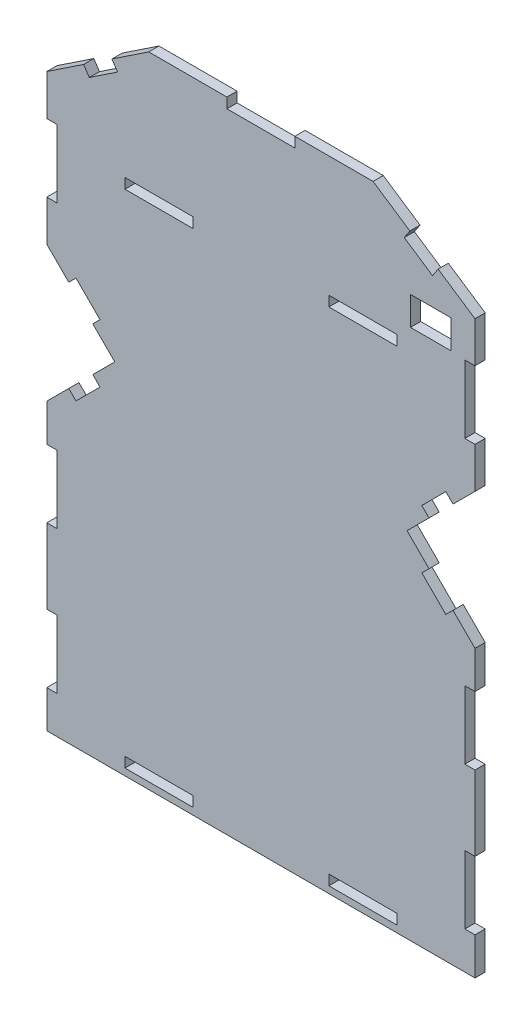
SolidWorks part; units mm, degrees
ref_plane "Front Plane" through (0, 0, 0) normal (0, 0, 1) x (1, 0, 0)
ref_plane "Top Plane" through (0, 0, 0) normal (0, 1, 0) x (1, 0, 0)
ref_plane "Right Plane" through (0, 0, 0) normal (1, 0, 0) x (0, 0, -1)
sketch "Sketch1" plane through (0, 0, 0) normal (0, 0, 1) x (1, 0, 0)
  line L0 (62.2747, 0) -> (62.2747, -11)
  line L1 (-33.7253, 104) -> (-10.7253, 104)
  line L2 (-63.7253, 84) -> (-63.7253, 72)
  line L3 (-63.7253, -84) -> (62.2747, -84)
  line L4 (62.2747, 84) -> (62.2747, 72)
  line L5 (-0.7253, -84) -> (-0.7253, -49.3815) construction
  line L6 (-63.7253, -84) -> (-63.7253, -80.5) construction
  line L7 (-63.7253, -80.5) -> (-60.7253, -80.5) construction
  line L8 (-63.7253, 84) -> (-52.8856, 91.2265)
  line L10 (-63.7253, 84) -> (-63.7253, 72) construction
  line L11 (-60.7253, -80.5) -> (-60.7253, -84) construction
  line L12 (-63.7253, 0) -> (-57.2608, 6.4645)
  line L13 (-43.7253, 20) -> (-50.1898, 26.4645)
  line L14 (62.2747, 0) -> (55.8102, 6.4645)
  line L15 (42.2747, 20) -> (48.7392, 26.4645)
  line L16 (-63.7253, 0) -> (-63.7253, -11)
  line L17 (62.2747, -80.5) -> (59.2747, -80.5) construction
  line L18 (-60.7253, -80.5) -> (59.2747, -80.5) construction
  line L19 (-0.7253, -80.5) -> (-60.7253, -80.5) construction
  line L20 (19.2747, -82) -> (19.2747, -79)
  line L21 (-40.7253, -82) -> (-20.7253, -82)
  line L22 (-40.7253, -82) -> (-40.7253, -79)
  line L23 (-40.7253, -79) -> (-20.7253, -79)
  line L24 (-20.7253, -82) -> (-20.7253, -79)
  line L25 (-40.7253, -82) -> (-20.7253, -79) construction
  line L26 (-40.7253, -79) -> (-20.7253, -82) construction
  line L27 (39.2747, -82) -> (19.2747, -82)
  line L28 (39.2747, -82) -> (39.2747, -79)
  line L29 (39.2747, -79) -> (19.2747, -79)
  line L30 (-63.7253, -84) -> (-62.221, -84) construction
  line L31 (-63.7253, -42) -> (-62.2253, -42) construction
  line L32 (-62.2253, -42) -> (-62.2253, 0) construction
  line L33 (-62.2253, 0) -> (-63.7253, 0) construction
  line L34 (-63.7253, -31) -> (-60.7253, -31)
  line L36 (-63.7253, -11) -> (-60.7253, -11)
  line L37 (-60.7253, -31) -> (-60.7253, -11)
  line L38 (-63.7253, -31) -> (-60.7253, -11) construction
  line L39 (-63.7253, -11) -> (-60.7253, -31) construction
  line L40 (-63.7253, -53) -> (-60.7253, -53)
  line L41 (-60.7253, -53) -> (-60.7253, -73)
  line L42 (-63.7253, -73) -> (-60.7253, -73)
  line L43 (-62.2253, -84) -> (-63.7253, -84) construction
  line L44 (62.2747, -53) -> (59.2747, -53)
  line L45 (59.2747, -53) -> (59.2747, -73)
  line L46 (62.2747, -73) -> (59.2747, -73)
  line L47 (62.2747, -31) -> (59.2747, -31)
  line L48 (62.2747, -11) -> (59.2747, -11)
  line L49 (59.2747, -31) -> (59.2747, -11)
  line L50 (-63.7253, -73) -> (-63.7253, -84)
  line L51 (62.2747, -73) -> (62.2747, -84)
  line L52 (62.2747, -31) -> (62.2747, -53)
  line L53 (-63.7253, -31) -> (-63.7253, -53)
  line L54 (-63.7253, 40) -> (-62.2253, 40) construction
  line L55 (-62.2253, 40) -> (-62.2253, 84) construction
  line L56 (-62.2253, 84) -> (-63.7253, 84) construction
  line L57 (-63.7253, 52) -> (-63.7253, 40)
  line L58 (-63.7253, 52) -> (-60.7253, 52)
  line L60 (-63.7253, 72) -> (-60.7253, 72)
  line L61 (-60.7253, 52) -> (-60.7253, 72)
  line L62 (-63.7253, 52) -> (-60.7253, 72) construction
  line L63 (-63.7253, 72) -> (-60.7253, 52) construction
  line L64 (-63.7253, 52) -> (-63.7253, 40) construction
  line L65 (62.2747, 52) -> (59.2747, 52)
  line L66 (59.2747, 52) -> (59.2747, 72)
  line L67 (62.2747, 72) -> (59.2747, 72)
  line L68 (62.2747, 52) -> (62.2747, 40)
  line L69 (-43.7253, 20) -> (-42.6646, 18.9393) construction
  line L70 (-63.7253, 0) -> (-62.6646, -1.0607) construction
  line L71 (-62.6646, -1.0607) -> (-42.6646, 18.9393) construction
  line L72 (-55.1395, 4.3431) -> (-57.2608, 6.4645)
  line L73 (-55.1395, 4.3431) -> (-48.0685, 11.4142)
  line L75 (-48.0685, 11.4142) -> (-50.1898, 13.5355)
  line L76 (-50.1898, 13.5355) -> (-43.7253, 20)
  line L77 (53.6889, 4.3431) -> (55.8102, 6.4645)
  line L78 (46.6178, 11.4142) -> (48.7392, 13.5355)
  line L79 (53.6889, 4.3431) -> (46.6178, 11.4142)
  line L80 (42.2747, 20) -> (5.8268, 20) construction
  line L81 (-55.1395, 35.6569) -> (-57.2608, 33.5355)
  line L82 (-48.0685, 28.5858) -> (-50.1898, 26.4645)
  line L83 (-55.1395, 35.6569) -> (-48.0685, 28.5858)
  line L84 (-57.2608, 33.5355) -> (-63.7253, 40)
  line L85 (46.6178, 28.5858) -> (48.7392, 26.4645)
  line L86 (53.6889, 35.6569) -> (55.8102, 33.5355)
  line L87 (53.6889, 35.6569) -> (46.6178, 28.5858)
  line L88 (55.8102, 33.5355) -> (62.2747, 40)
  line L89 (48.7392, 13.5355) -> (42.2747, 20)
  line L90 (-63.7253, 84) -> (-52.8856, 91.2265) construction
  line L92 (-52.8856, 91.2265) -> (-51.2215, 88.7303)
  line L93 (-44.5651, 96.7735) -> (-42.901, 94.2774)
  line L94 (-51.2215, 88.7303) -> (-42.901, 94.2774)
  line L95 (-44.5651, 96.7735) -> (-33.7253, 104)
  line L96 (-44.5651, 96.7735) -> (-33.7253, 104) construction
  line L97 (-33.7253, 104) -> (-63.7253, 84) construction
  line L98 (-48.7253, 94) -> (-47.0612, 91.5038) construction
  line L99 (51.4349, 91.2265) -> (49.7708, 88.7303)
  line L100 (49.7708, 88.7303) -> (41.4503, 94.2774)
  line L101 (43.1144, 96.7735) -> (41.4503, 94.2774)
  line L102 (32.2747, 104) -> (43.1144, 96.7735)
  line L103 (62.2747, 84) -> (51.4349, 91.2265)
  line L104 (-33.7253, 104) -> (-33.7253, 102.5) construction
  line L105 (-33.7253, 102.5) -> (32.2747, 102.5) construction
  line L106 (32.2747, 102.5) -> (32.2747, 104) construction
  line L107 (-10.7253, 101) -> (9.2747, 101)
  line L108 (-10.7253, 101) -> (-10.7253, 104)
  line L110 (9.2747, 101) -> (9.2747, 104)
  line L111 (-10.7253, 101) -> (9.2747, 104) construction
  line L112 (-10.7253, 104) -> (9.2747, 101) construction
  line L113 (9.2747, 104) -> (32.2747, 104)
  line L114 (-63.7253, 84) -> (62.2747, 84) construction
  line L115 (-0.7253, 84) -> (-0.7253, 67) construction
  line L116 (-0.7253, 67) -> (-60.7253, 67) construction
  line L117 (39.2747, 65.5) -> (39.2747, 68.5)
  line L118 (-40.7253, 65.5) -> (-20.7253, 65.5)
  line L119 (-40.7253, 65.5) -> (-40.7253, 68.5)
  line L120 (-40.7253, 68.5) -> (-20.7253, 68.5)
  line L121 (-20.7253, 65.5) -> (-20.7253, 68.5)
  line L122 (-40.7253, 65.5) -> (-20.7253, 68.5) construction
  line L123 (-40.7253, 68.5) -> (-20.7253, 65.5) construction
  line L124 (39.2747, 65.5) -> (19.2747, 65.5)
  line L125 (19.2747, 65.5) -> (19.2747, 68.5)
  line L126 (39.2747, 68.5) -> (19.2747, 68.5)
  line L127 (59.2747, 68.5) -> (59.2747, 76.5) construction
  line L128 (59.2747, 84) -> (59.2747, 72) construction
  line L129 (59.2747, 68.5) -> (49.2747, 68.5) construction
  line L130 (39.2747, 68.5) -> (59.2747, 68.5) construction
  line L131 (49.2747, 68.5) -> (49.2747, 76.5) construction
  line L132 (49.2747, 76.5) -> (59.2747, 76.5) construction
  line L134 (43.2747, 80.7) -> (55.2747, 80.7)
  line L135 (43.2747, 80.7) -> (43.2747, 72.3)
  line L136 (43.2747, 72.3) -> (55.2747, 72.3)
  line L137 (55.2747, 80.7) -> (55.2747, 72.3)
  line L138 (43.2747, 80.7) -> (55.2747, 72.3) construction
  line L139 (43.2747, 72.3) -> (55.2747, 80.7) construction
  point P0 (0, 0)
  point P20 (-30.7253, -80.5)
  point P31 (-62.2253, -21)
  point P53 (-62.2253, 62)
  point P67 (-52.6646, 8.9393)
  point P94 (-0.7253, 102.5)
  point P103 (-30.7253, 67)
  dimension "D1" = 84
  dimension "D2" = 126
  dimension "D3" = 20
  dimension "D4" = 30
  dimension "D5" = 20
  dimension "D6" = 20
  dimension "D7" = 44
  dimension "D8" = 20
  dimension "D9" = 30
  dimension "D10" = 20
  dimension "D11" = 20
  dimension "D12" = 84
  dimension "D13" = 44
  dimension "D14" = 20
  dimension "D15" = 3
  dimension "D16" = 3.5
  dimension "D17" = 20
  dimension "D18" = 3
  dimension "D19" = 1.5
  dimension "D20" = 20
  dimension "D21" = 3
  dimension "D22" = 1.5
  dimension "D23" = 1.5
  dimension "D24" = 20
  dimension "D25" = 3
  dimension "D26" = 10
  dimension "D27" = 1.5
  dimension "D28" = 48.0685
  dimension "D29" = 10
  dimension "D30" = 3
  dimension "D31" = 17
  dimension "D32" = 20
  dimension "D33" = 3
  dimension "D34" = 3
  dimension "D35" = 20
  dimension "D36" = 60
  dimension "D37" = 8
  dimension "D38" = 10
  dimension "D39" = 8.4
  dimension "D40" = 12
extrude "Boss-Extrude1" add sketch "Sketch1" along normal blind 3
